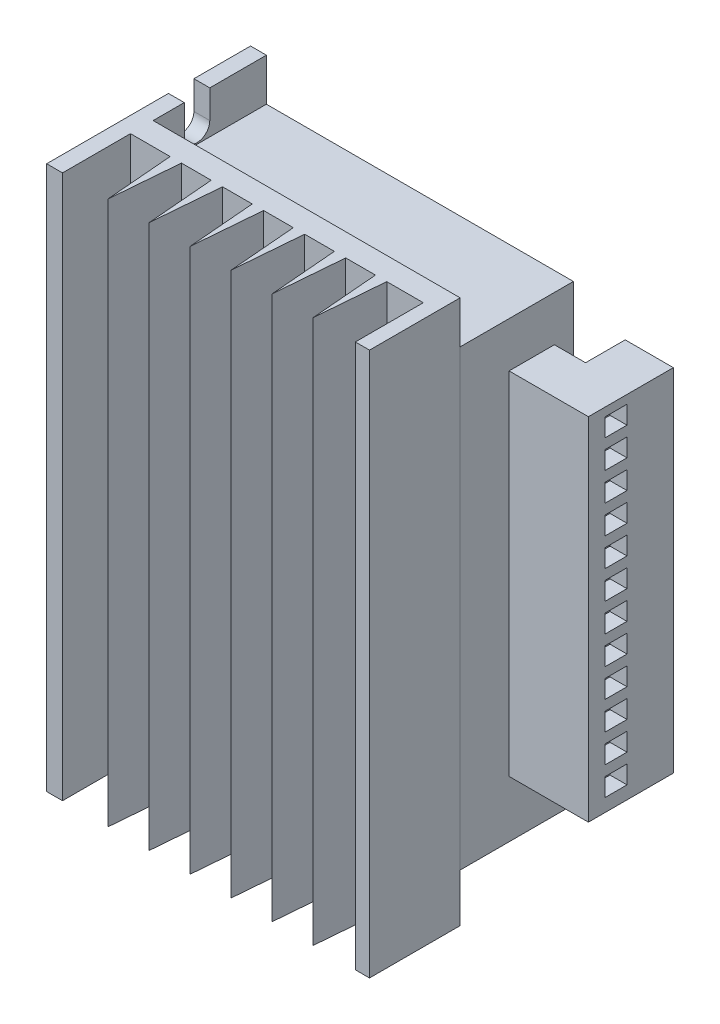
SolidWorks part; units mm, degrees
ref_plane "Front Plane" through (0, 0, 0) normal (0, 0, 1) x (1, 0, 0)
ref_plane "Top Plane" through (0, 0, 0) normal (0, 1, 0) x (1, 0, 0)
ref_plane "Right Plane" through (0, 0, 0) normal (1, 0, 0) x (0, 0, -1)
sketch "Sketch1" plane through (0, 0, 0) normal (0, 1, 0) x (1, 0, 0)
  line L0 (2.8, 16) -> (57, 16)
  line L1 (54.5, 0) -> (57, 0)
  line L2 (0, 36) -> (0, 0)
  line L3 (2.8, 12) -> (9.8, 12)
  line L4 (57, 0) -> (57, 16)
  line L5 (0, 0) -> (2.8, 0)
  line L7 (0, 36) -> (2.8, 36)
  line L8 (2.8, 16) -> (2.8, 36)
  line L9 (2.8, 12) -> (2.8, 0)
  line L10 (18.05, 0) -> (17.05, 12)
  line L11 (18.05, 0) -> (19.05, 12)
  line L12 (25.3, 0) -> (24.3, 12)
  line L13 (10.8, 0) -> (9.8, 12)
  line L14 (10.8, 0) -> (11.8, 12)
  line L15 (25.3, 0) -> (26.3, 12)
  line L16 (32.55, 0) -> (31.55, 12)
  line L17 (32.55, 0) -> (33.55, 12)
  line L18 (39.8, 0) -> (38.8, 12)
  line L19 (39.8, 0) -> (40.8, 12)
  line L20 (47.05, 0) -> (46.05, 12)
  line L21 (47.05, 0) -> (48.05, 12)
  line L22 (54.5, 0) -> (54.5, 12)
  line L23 (54.5, 0) -> (54.5, 16) construction
  line L24 (2.8, 12) -> (57, 12) construction
  line L25 (48.05, 12) -> (54.5, 12)
  line L26 (40.8, 12) -> (46.05, 12)
  line L27 (33.55, 12) -> (38.8, 12)
  line L28 (26.3, 12) -> (31.55, 12)
  line L29 (19.05, 12) -> (24.3, 12)
  line L30 (11.8, 12) -> (17.05, 12)
  dimension "D1" = 6
extrude "Boss-Extrude1" add sketch "Sketch1" along normal blind 96
sketch "Sketch2" plane through (2.8, 0, 0) normal (1, 0, 0) x (0, 0, -1)
  line L4 (16, 96) -> (16, 0) construction
  line L5 (36, 96) -> (36, 0) construction
  line L6 (16, 88.5) -> (36, 88.5)
  line L7 (16, 88.5) -> (16, 8.5)
  line L8 (16, 8.5) -> (36, 8.5)
  line L9 (36, 88.5) -> (36, 8.5)
  line M3 (36, 0) -> (36, 96)
  line M5 (16, 96) -> (16, 0)
extrude "Boss-Extrude2" add sketch "Sketch2" along normal blind 54.2 separate body contours L8 L6 M5 M3 region at (2.8, 48.5, -26)
sketch "Sketch8" plane through (2.8, 0, 0) normal (1, 0, 0) x (0, 0, -1)
  line L0 (26, 96) -> (26, 91)
  line L1 (16, 96) -> (36, 96) construction
  line L2 (21.5, 96) -> (21.5, 91)
  line L3 (21.5, 96) -> (26, 96)
  line L6 (21.5, 0) -> (26, 0)
  line L7 (21.5, 0) -> (21.5, 5)
  line L8 (26, 0) -> (26, 5)
  arc A0 (26, 91) -> (21.5, 91) centre (23.75, 91) cw
  arc A1 (26, 5) -> (21.5, 5) centre (23.75, 5) ccw
  line M6 (16, 0) -> (36, 0)
  line M8 (36, 96) -> (16, 96)
extrude "Cut-Extrude1" cut sketch "Sketch8" against normal blind 4 contours A0 L0 L2 M8 | L8 A1 L7 M6 region at (2.8, 92.5978, -23.75) region at (2.8, 3.4022, -23.75)
sketch "Sketch9" plane through (57, 0, 0) normal (1, 0, 0) x (0, 0, -1)
  line L0 (16, 88.5) -> (36, 88.5) construction
  line L1 (24.6447, 80.5) -> (32.6447, 80.5)
  line L2 (24.6447, 80.5) -> (24.6447, 18.5)
  line L3 (24.6447, 18.5) -> (32.6447, 18.5)
  line L4 (32.6447, 80.5) -> (32.6447, 18.5)
  dimension "D1" = 62
  dimension "D2" = 8
  dimension "D3" = 8
extrude "Boss-Extrude4" add sketch "Sketch9" along normal blind 14 separate body
sketch "Sketch10" plane through (71, 0, 0) normal (1, 0, 0) x (0, 0, -1)
  line L2 (24.6447, 80.5) -> (39.6447, 80.5)
  line L3 (24.6447, 80.5) -> (24.6447, 18.5)
  line L4 (24.6447, 18.5) -> (39.6447, 18.5)
  line L7 (39.6447, 80.5) -> (39.6447, 18.5)
extrude "Boss-Extrude5" add sketch "Sketch10" against normal blind 8.5
sketch "Sketch11" plane through (0, 0, -39.6447) normal (0, 0, -1) x (-1, 0, 0)
  circle A0 centre (-66.1245, 77.4968) radius 1.6
  circle A1 centre (-66.1245, 72.4968) radius 1.6
  circle A2 centre (-66.1245, 67.4968) radius 1.6
  circle A3 centre (-66.1245, 62.4968) radius 1.6
  circle A4 centre (-66.1245, 57.4968) radius 1.6
  circle A5 centre (-66.1245, 52.4968) radius 1.6
  circle A6 centre (-66.1245, 47.4968) radius 1.6
  circle A7 centre (-66.1245, 42.4968) radius 1.6
  circle A8 centre (-66.1245, 37.4968) radius 1.6
  circle A9 centre (-66.1245, 32.4968) radius 1.6
  circle A10 centre (-66.1245, 27.4968) radius 1.6
  circle A11 centre (-66.1245, 22.4968) radius 1.6
extrude "Cut-Extrude2" cut sketch "Sketch11" against normal blind 1
sketch "Sketch13" plane through (0, 0, -38.6447) normal (0, 0, -1) x (-1, 0, 0)
  circle A0 centre (-66.1245, 77.4968) radius 1.5085
  circle A1 centre (-66.1245, 72.4968) radius 1.5085
  circle A2 centre (-66.1245, 67.4968) radius 1.5085
  circle A3 centre (-66.1245, 62.4968) radius 1.5085
  circle A4 centre (-66.1245, 57.4968) radius 1.5085
  circle A5 centre (-66.1245, 52.4968) radius 1.5085
  circle A6 centre (-66.1245, 47.4968) radius 1.5085
  circle A7 centre (-66.1245, 42.4968) radius 1.5085
  circle A8 centre (-66.1245, 37.4968) radius 1.5085
  circle A9 centre (-66.1245, 32.4968) radius 1.5085
  circle A10 centre (-66.1245, 27.4968) radius 1.5085
  circle A11 centre (-66.1245, 22.4968) radius 1.5085
extrude "Boss-Extrude6" add sketch "Sketch13" along normal blind 0.5 separate body
fillet "Fillet19" radius 0.5 1 edges at (66.1245, 79.0053, -39.1447)
fillet "Fillet20" radius 0.5 1 edges at (66.1245, 74.0053, -39.1447)
fillet "Fillet21" radius 0.5 1 edges at (66.1245, 69.0053, -39.1447)
fillet "Fillet22" radius 0.5 1 edges at (66.1245, 64.0053, -39.1447)
fillet "Fillet23" radius 0.5 1 edges at (66.1245, 59.0053, -39.1447)
fillet "Fillet24" radius 0.5 1 edges at (66.1245, 54.0053, -39.1447)
fillet "Fillet25" radius 0.5 1 edges at (66.1245, 49.0053, -39.1447)
fillet "Fillet26" radius 0.5 1 edges at (66.1245, 44.0053, -39.1447)
fillet "Fillet27" radius 0.5 1 edges at (66.1245, 39.0053, -39.1447)
fillet "Fillet28" radius 0.5 1 edges at (66.1245, 34.0053, -39.1447)
fillet "Fillet29" radius 0.5 1 edges at (66.1245, 29.0053, -39.1447)
fillet "Fillet30" radius 0.5 1 edges at (66.1245, 24.0053, -39.1447)
sketch "Sketch15" plane through (0, 0, -39.1447) normal (0, 0, -1) x (-1, 0, 0)
  line L0 (-65.5267, 71.1211) -> (-66.2369, 73.9926)
  line L1 (-65.5267, 76.1211) -> (-66.2369, 78.9926)
  line L2 (-66.012, 76.001) -> (-66.7223, 78.8725)
  line L3 (-66.012, 71.001) -> (-66.7223, 73.8725)
  line L4 (-65.5267, 66.1211) -> (-66.2369, 68.9926)
  line L5 (-66.012, 66.001) -> (-66.7223, 68.8725)
  line L6 (-65.5267, 61.1211) -> (-66.2369, 63.9926)
  line L7 (-66.012, 61.001) -> (-66.7223, 63.8725)
  line L8 (-65.5267, 56.1211) -> (-66.2369, 58.9926)
  line L9 (-66.012, 56.001) -> (-66.7223, 58.8725)
  line L10 (-65.5267, 51.1211) -> (-66.2369, 53.9926)
  line L11 (-66.012, 51.001) -> (-66.7223, 53.8725)
  line L12 (-65.5267, 46.1211) -> (-66.2369, 48.9926)
  line L13 (-66.012, 46.001) -> (-66.7223, 48.8725)
  line L14 (-65.5267, 41.1211) -> (-66.2369, 43.9926)
  line L15 (-66.012, 41.001) -> (-66.7223, 43.8725)
  line L16 (-65.5267, 36.1211) -> (-66.2369, 38.9926)
  line L17 (-66.012, 36.001) -> (-66.7223, 38.8725)
  line L18 (-65.5267, 31.1211) -> (-66.2369, 33.9926)
  line L19 (-66.012, 31.001) -> (-66.7223, 33.8725)
  line L20 (-65.5267, 26.1211) -> (-66.2369, 28.9926)
  line L21 (-66.012, 26.001) -> (-66.7223, 28.8725)
  line L22 (-65.5267, 21.1211) -> (-66.2369, 23.9926)
  line L23 (-66.012, 21.001) -> (-66.7223, 23.8725)
  arc A0 (-66.2369, 78.9926) -> (-66.7223, 78.8725) centre (-66.1245, 77.4968) ccw
  arc A1 (-66.012, 76.001) -> (-65.5267, 76.1211) centre (-66.1245, 77.4968) ccw
  arc A2 (-66.2369, 73.9926) -> (-66.7223, 73.8725) centre (-66.1245, 72.4968) ccw
  arc A3 (-66.012, 71.001) -> (-65.5267, 71.1211) centre (-66.1245, 72.4968) ccw
  arc A4 (-66.2369, 68.9926) -> (-66.7223, 68.8725) centre (-66.1245, 67.4968) ccw
  arc A5 (-66.012, 66.001) -> (-65.5267, 66.1211) centre (-66.1245, 67.4968) ccw
  arc A6 (-66.2369, 63.9926) -> (-66.7223, 63.8725) centre (-66.1245, 62.4968) ccw
  arc A7 (-66.012, 61.001) -> (-65.5267, 61.1211) centre (-66.1245, 62.4968) ccw
  arc A8 (-66.2369, 58.9926) -> (-66.7223, 58.8725) centre (-66.1245, 57.4968) ccw
  arc A9 (-66.012, 56.001) -> (-65.5267, 56.1211) centre (-66.1245, 57.4968) ccw
  arc A10 (-66.2369, 53.9926) -> (-66.7223, 53.8725) centre (-66.1245, 52.4968) ccw
  arc A11 (-66.012, 51.001) -> (-65.5267, 51.1211) centre (-66.1245, 52.4968) ccw
  arc A12 (-66.2369, 48.9926) -> (-66.7223, 48.8725) centre (-66.1245, 47.4968) ccw
  arc A13 (-66.012, 46.001) -> (-65.5267, 46.1211) centre (-66.1245, 47.4968) ccw
  arc A14 (-66.2369, 43.9926) -> (-66.7223, 43.8725) centre (-66.1245, 42.4968) ccw
  arc A15 (-66.012, 41.001) -> (-65.5267, 41.1211) centre (-66.1245, 42.4968) ccw
  arc A16 (-66.2369, 38.9926) -> (-66.7223, 38.8725) centre (-66.1245, 37.4968) ccw
  arc A17 (-66.012, 36.001) -> (-65.5267, 36.1211) centre (-66.1245, 37.4968) ccw
  arc A18 (-66.2369, 33.9926) -> (-66.7223, 33.8725) centre (-66.1245, 32.4968) ccw
  arc A19 (-66.012, 31.001) -> (-65.5267, 31.1211) centre (-66.1245, 32.4968) ccw
  arc A20 (-66.2369, 28.9926) -> (-66.7223, 28.8725) centre (-66.1245, 27.4968) ccw
  arc A21 (-66.012, 26.001) -> (-65.5267, 26.1211) centre (-66.1245, 27.4968) ccw
  arc A22 (-66.2369, 23.9926) -> (-66.7223, 23.8725) centre (-66.1245, 22.4968) ccw
  arc A23 (-66.012, 21.001) -> (-65.5267, 21.1211) centre (-66.1245, 22.4968) ccw
extrude "Cut-Extrude4" cut sketch "Sketch15" against normal blind 0.25
sketch "Sketch16" plane through (71, 0, 0) normal (1, 0, 0) x (0, 0, -1)
  line L1 (27.5359, 79) -> (31.4621, 79)
  line L2 (27.5359, 79) -> (27.5359, 75.8)
  line L3 (27.5359, 75.8) -> (31.4621, 75.8)
  line L4 (31.4621, 79) -> (31.4621, 75.8)
  line L6 (27.5359, 74) -> (31.4621, 74)
  line L7 (27.5359, 74) -> (27.5359, 70.8)
  line L8 (27.5359, 70.8) -> (31.4621, 70.8)
  line L9 (31.4621, 74) -> (31.4621, 70.8)
  line L10 (27.5359, 69) -> (31.4621, 69)
  line L11 (27.5359, 69) -> (27.5359, 65.8)
  line L12 (27.5359, 65.8) -> (31.4621, 65.8)
  line L13 (31.4621, 69) -> (31.4621, 65.8)
  line L14 (27.5359, 64) -> (31.4621, 64)
  line L15 (27.5359, 64) -> (27.5359, 60.8)
  line L16 (27.5359, 60.8) -> (31.4621, 60.8)
  line L17 (31.4621, 64) -> (31.4621, 60.8)
  line L18 (27.5359, 59) -> (31.4621, 59)
  line L19 (27.5359, 59) -> (27.5359, 55.8)
  line L20 (27.5359, 55.8) -> (31.4621, 55.8)
  line L21 (31.4621, 59) -> (31.4621, 55.8)
  line L22 (27.5359, 54) -> (31.4621, 54)
  line L23 (27.5359, 54) -> (27.5359, 50.8)
  line L24 (27.5359, 50.8) -> (31.4621, 50.8)
  line L25 (31.4621, 54) -> (31.4621, 50.8)
  line L26 (27.5359, 49) -> (31.4621, 49)
  line L27 (27.5359, 49) -> (27.5359, 45.8)
  line L28 (27.5359, 45.8) -> (31.4621, 45.8)
  line L29 (31.4621, 49) -> (31.4621, 45.8)
  line L30 (27.5359, 44) -> (31.4621, 44)
  line L31 (27.5359, 44) -> (27.5359, 40.8)
  line L32 (27.5359, 40.8) -> (31.4621, 40.8)
  line L33 (31.4621, 44) -> (31.4621, 40.8)
  line L34 (27.5359, 39) -> (31.4621, 39)
  line L35 (27.5359, 39) -> (27.5359, 35.8)
  line L36 (27.5359, 35.8) -> (31.4621, 35.8)
  line L37 (31.4621, 39) -> (31.4621, 35.8)
  line L38 (27.5359, 34) -> (31.4621, 34)
  line L39 (27.5359, 34) -> (27.5359, 30.8)
  line L40 (27.5359, 30.8) -> (31.4621, 30.8)
  line L41 (31.4621, 34) -> (31.4621, 30.8)
  line L42 (27.5359, 29) -> (31.4621, 29)
  line L43 (27.5359, 29) -> (27.5359, 25.8)
  line L44 (27.5359, 25.8) -> (31.4621, 25.8)
  line L45 (31.4621, 29) -> (31.4621, 25.8)
  line L46 (27.5359, 24) -> (31.4621, 24)
  line L47 (27.5359, 24) -> (27.5359, 20.8)
  line L48 (27.5359, 20.8) -> (31.4621, 20.8)
  line L49 (31.4621, 24) -> (31.4621, 20.8)
extrude "Cut-Extrude5" cut sketch "Sketch16" against normal blind 3
